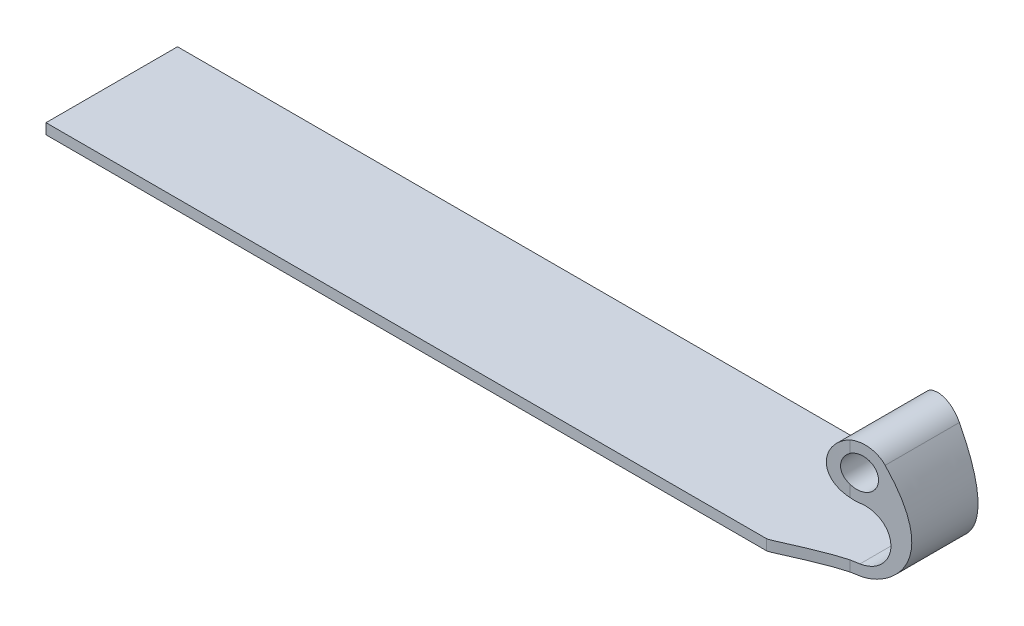
SolidWorks part; units mm, degrees
ref_plane "Front Plane" through (0, 0, 0) normal (0, 0, 1) x (1, 0, 0)
ref_plane "Top Plane" through (0, 0, 0) normal (0, 1, 0) x (1, 0, 0)
ref_plane "Right Plane" through (0, 0, 0) normal (1, 0, 0) x (0, 0, -1)
sketch "Sketch1" plane through (0, 0, 0) normal (0, 1, 0) x (1, 0, 0)
  line L1 (-38.1, -6.35) -> (38.1, -6.35)
  line L2 (-38.1, -6.35) -> (-38.1, 6.35)
  line L3 (-38.1, 6.35) -> (38.1, 6.35)
  line L4 (38.1, -6.35) -> (38.1, 6.35)
  line L5 (-38.1, -6.35) -> (38.1, 6.35) construction
  line L6 (-38.1, 6.35) -> (38.1, -6.35) construction
  point P0 (0, 0)
  dimension "D1" = 12.7
  dimension "D2" = 76.2
extrude "Boss-Extrude1" add sketch "Sketch1" along normal blind 1.016
sketch "Sketch2" plane through (0, 0, -6.35) normal (0, 0, -1) x (-1, 0, 0)
  line L1 (-38.1, 0) -> (38.1, 0) construction
  line L2 (-38.1, 0) -> (-40.0156, 0) construction
  line L3 (-40.0156, 0) -> (-42.8226, 1.8153) construction
  line L4 (-42.8226, 1.8153) -> (-43.8111, 4.9975) construction
  line L5 (-43.8111, 4.9975) -> (-40.1686, 10.1099) construction
  line L7 (-38.1, 1.016) -> (38.1, 1.016) construction
  line L8 (38.1, 1.016) -> (38.1, 0)
  line L9 (-38.1, 0) -> (38.1, 0)
  line L11 (38.1, 1.016) -> (38.1, 0) construction
  line L13 (-38.1, 1.016) -> (38.1, 1.016)
  arc A1 (-38.1, 6.096) -> (-40.1686, 10.1099) centre (-38.1, 8.636) ccw
  circle A2 centre (-38.1, 8.636) radius 1.524
  arc A6 (-38.1, 1.016) -> (-38.1, 6.096) centre (-38.1, 3.556) cw
  spline S0 degree 4 poles (-38.1, 0) (-40.0156, 0) (-42.8226, 1.8153) (-43.8111, 4.9975) (-40.1686, 10.1099) knots 0 0 0 0 0 1 1 1 1 1
  point P8 (-38.1, 1.016)
  dimension "D1" = 2.54
  dimension "D2" = 5.08
  dimension "D3" = 1.016
extrude "Boss-Extrude2" add sketch "Sketch2" against normal through all
sketch "Sketch3" plane through (0, 1.016, 0) normal (0, -1, 0) x (1, 0, 0)
  line L0 (24.4723, 6.35) -> (42.3541, 3.197)
  line L1 (-38.1, 6.35) -> (38.1, 6.35) construction
  line L2 (42.3541, 0) -> (38.1, 0) construction
  line L3 (42.3541, -6.35) -> (42.3541, 6.35) construction
  line L4 (38.1, 6.35) -> (38.1, -6.35) construction
  line L5 (24.4723, -6.35) -> (42.3541, -3.197)
  line L6 (24.4723, 6.35) -> (42.3541, 6.35)
  line L7 (42.3541, 6.35) -> (38.1, 6.35) construction
  line L8 (42.3541, 6.35) -> (42.3541, 3.197)
  line L9 (42.3541, -3.197) -> (42.3541, -6.35)
  line L10 (38.1, -6.35) -> (42.3541, -6.35) construction
  line L11 (42.3541, -6.35) -> (24.4723, -6.35)
  line L12 (39.2057, -3.7521) -> (36.3577, -3.8761) construction
  line L13 (36.3577, -3.8761) -> (31.9938, -6.35) construction
  line L14 (31.9938, -6.35) -> (31.4619, -6.35) construction
  line L15 (39.2057, 3.7521) -> (36.3577, 3.8761) construction
  line L16 (36.3577, 3.8761) -> (31.9938, 6.35) construction
  line L17 (31.9938, 6.35) -> (31.4619, 6.35) construction
  circle A0 centre (38.5441, 0) radius 3.81
  spline S0 degree 3 poles (39.2057, -3.7521) (36.3577, -3.8761) (31.9938, -6.35) (31.4619, -6.35) knots 0 0 0 0 1 1 1 1
  spline S1 degree 3 poles (39.2057, 3.7521) (36.3577, 3.8761) (31.9938, 6.35) (31.4619, 6.35) knots 0 0 0 0 1 1 1 1
  line M26 (38.1, 6.35) -> (38.1, -6.35)
  line M27 (38.1, -6.35) -> (-38.1, -6.35)
  dimension "D2" = 7.62
  dimension "D1" = 10
extrude "Cut-Extrude1" cut sketch "Sketch3" against normal through all and the other way blind 10 contours S0 L5 M26 M27 | L9 L11 L5 M26 | L6 L8 L0 M26 | L0 S1 L6 M26 region at (40.3228, 1.016, 4.9526) region at (35.8593, 1.016, 5.4807) region at (40.3228, 1.016, -4.9526) region at (35.8593, 1.016, -5.4807)
